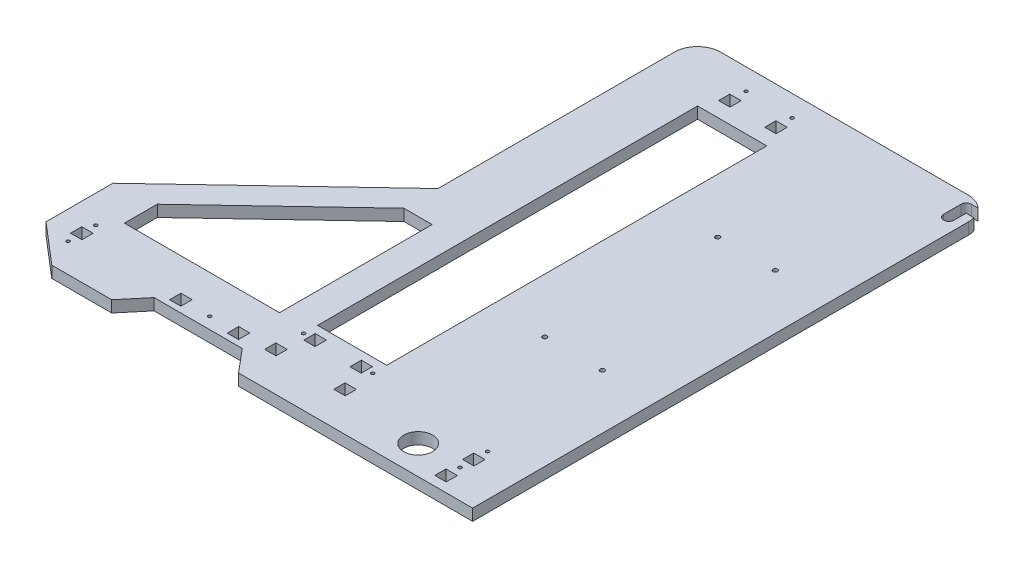
SolidWorks part; units mm, degrees
ref_plane "Front Plane" through (0, 0, 0) normal (0, 0, 1) x (1, 0, 0)
ref_plane "Top Plane" through (0, 0, 0) normal (0, 1, 0) x (1, 0, 0)
ref_plane "Right Plane" through (0, 0, 0) normal (1, 0, 0) x (0, 0, -1)
sketch "Sketch1" plane through (0, 0, 0) normal (0, 1, 0) x (1, 0, 0)
  line L0 (0, 0) -> (-235, 0)
  line L1 (-235, 0) -> (-235, -225)
  line L2 (-235, -225) -> (-380, -362)
  line L3 (-380, -362) -> (-380, -420)
  line L4 (-380, -420) -> (-345, -450)
  line L5 (-345, -450) -> (-293, -450)
  line L6 (-293, -450) -> (-263.6315, -415)
  line L7 (-263.6315, -415) -> (-212.3685, -415)
  line L8 (-212.3685, -415) -> (-183, -450)
  line L9 (-183, -450) -> (0, -450)
  line L10 (0, 0) -> (0, -450)
  line L12 (-293, -450) -> (-183, -450) construction
  dimension "D3" = 235
  dimension "D5" = 58
  dimension "D13" = 190
  dimension "D7" = 35
  dimension "D15" = 52
  dimension "D12" = 30
  dimension "D10" = 35
  dimension "D6" = 380
  dimension "D4" = 450
  dimension "D2" = 50
  dimension "D8" = 50
  dimension "D9" = 110
extrude "Boss-Extrude1" add sketch "Sketch1" along normal blind 10
sketch "Sketch16" plane through (0, 10, 0) normal (0, 1, 0) x (1, 0, 0)
  line L0 (0, -450) -> (20, -450)
  line L1 (20, -450) -> (20, 0)
  line L2 (20, 0) -> (0, 0)
  line L3 (0, 0) -> (0, -450)
  dimension "D1" = 20
  dimension "D2" = 90
extrude "Boss-Extrude2" add sketch "Sketch16" against normal through all
sketch "Sketch2" plane through (0, 10, 0) normal (0, 1, 0) x (1, 0, 0)
  line L0 (-235, -225) -> (-235, -415) construction
  line L1 (-263.6315, -415) -> (-212.3685, -415) construction
  line L2 (-345, -450) -> (-345, -328.931) construction
  line L3 (-235, -225) -> (-380, -362) construction
  line L4 (-345, -358.5097) -> (-235, -254.5787)
  line L5 (-235, -254.5787) -> (-210.5, -254.5787)
  line L6 (-210.5, -254.5787) -> (-210.5, -387)
  line L7 (-210.5, -387) -> (-345, -387)
  line L8 (-345, -387) -> (-345, -358.5097)
  line L9 (0, -450) -> (0, 0) construction
  line L10 (-184.5, -380) -> (-124.5, -380)
  line L11 (-184.5, -380) -> (-184.5, -50.425)
  line L12 (-184.5, -50.425) -> (-124.5, -50.425)
  line L13 (-124.5, -380) -> (-124.5, -50.425)
  line L14 (-124.5, -392.1) -> (-184.5, -392.1) construction
  line L15 (-16, -450) -> (-16, 0) construction
  line L16 (20, 0) -> (-235, 0) construction
  line L17 (-355.9, -440.6571) -> (-355.9, -339.2297) construction
  line L18 (-20.925, -441.85) -> (-11.075, -441.85)
  line L19 (-20.925, -441.85) -> (-20.925, -432.15)
  line L20 (-20.925, -432.15) -> (-11.075, -432.15)
  line L21 (-11.075, -441.85) -> (-11.075, -432.15)
  line L22 (-20.925, -441.85) -> (-11.075, -432.15) construction
  line L23 (-20.925, -432.15) -> (-11.075, -441.85) construction
  line L24 (-20.925, -417.85) -> (-11.075, -417.85)
  line L25 (-20.925, -417.85) -> (-20.925, -408.15)
  line L26 (-20.925, -408.15) -> (-11.075, -408.15)
  line L27 (-11.075, -417.85) -> (-11.075, -408.15)
  line L28 (-20.925, -417.85) -> (-11.075, -408.15) construction
  line L29 (-20.925, -408.15) -> (-11.075, -417.85) construction
  line L30 (-380, -420) -> (-345, -450) construction
  line L32 (-350.975, -408.15) -> (-360.825, -408.15)
  line L33 (-350.975, -408.15) -> (-350.975, -417.85)
  line L34 (-350.975, -417.85) -> (-360.825, -417.85)
  line L35 (-360.825, -408.15) -> (-360.825, -417.85)
  line L36 (-350.975, -408.15) -> (-360.825, -417.85) construction
  line L37 (-350.975, -417.85) -> (-360.825, -408.15) construction
  line L38 (-183, -450) -> (20, -450) construction
  line L39 (-183, -450) -> (20, -450) construction
  line L40 (-173.749, -32.425) -> (-113.749, -32.425) construction
  line L41 (-154.5, -50.425) -> (-154.5, -32.425) construction
  line L42 (-179.425, -27.575) -> (-169.575, -27.575)
  line L43 (-179.425, -27.575) -> (-179.425, -37.275)
  line L44 (-179.425, -37.275) -> (-169.575, -37.275)
  line L45 (-169.575, -27.575) -> (-169.575, -37.275)
  line L46 (-179.425, -27.575) -> (-169.575, -37.275) construction
  line L47 (-179.425, -37.275) -> (-169.575, -27.575) construction
  line L48 (-129.575, -37.275) -> (-139.425, -27.575) construction
  line L49 (-129.575, -27.575) -> (-139.425, -37.275) construction
  line L50 (-139.425, -27.575) -> (-139.425, -37.275)
  line L51 (-129.575, -37.275) -> (-139.425, -37.275)
  line L52 (-129.575, -27.575) -> (-129.575, -37.275)
  line L53 (-129.575, -27.575) -> (-139.425, -27.575)
  line L54 (-174.5, -32.425) -> (-174.5, -18.425) construction
  line L55 (-134.5, -32.425) -> (-134.5, -18.425) construction
  line L56 (-154.5, -380) -> (-154.5, -450) construction
  line L57 (-174.5, -392.1) -> (-134.5, -392.1) construction
  line L58 (-129.65, -397.025) -> (-139.35, -387.175) construction
  line L59 (-179.35, -387.175) -> (-169.65, -387.175)
  line L60 (-179.35, -387.175) -> (-179.35, -397.025)
  line L61 (-179.35, -397.025) -> (-169.65, -397.025)
  line L62 (-169.65, -387.175) -> (-169.65, -397.025)
  line L63 (-179.35, -387.175) -> (-169.65, -397.025) construction
  line L64 (-179.35, -397.025) -> (-169.65, -387.175) construction
  line L65 (-129.65, -387.175) -> (-139.35, -397.025) construction
  line L66 (-139.35, -387.175) -> (-139.35, -397.025)
  line L67 (-129.65, -397.025) -> (-139.35, -397.025)
  line L68 (-129.65, -387.175) -> (-129.65, -397.025)
  line L69 (-129.65, -387.175) -> (-139.35, -387.175)
  line L70 (-119.575, -420.95) -> (-129.425, -411.25) construction
  line L71 (-189.425, -411.25) -> (-179.575, -411.25)
  line L72 (-189.425, -411.25) -> (-189.425, -420.95)
  line L73 (-189.425, -420.95) -> (-179.575, -420.95)
  line L74 (-179.575, -411.25) -> (-179.575, -420.95)
  line L75 (-189.425, -411.25) -> (-179.575, -420.95) construction
  line L76 (-189.425, -420.95) -> (-179.575, -411.25) construction
  line L77 (-119.575, -411.25) -> (-129.425, -420.95) construction
  line L78 (-129.425, -411.25) -> (-129.425, -420.95)
  line L79 (-119.575, -420.95) -> (-129.425, -420.95)
  line L80 (-119.575, -411.25) -> (-119.575, -420.95)
  line L81 (-119.575, -411.25) -> (-129.425, -411.25)
  line L82 (-360.825, -408.15) -> (-11.075, -408.15) construction
  circle A0 centre (-16, -425) radius 1.45
  circle A1 centre (-16, -401) radius 1.45
  circle A2 centre (-355.9, -425) radius 1.45
  circle A3 centre (-355.9, -401) radius 1.45
  circle A4 centre (-174.5, -18.425) radius 1.45
  circle A5 centre (-134.5, -18.425) radius 1.45
  circle A6 centre (-124.5, -392.1) radius 1.45
  circle A7 centre (-184.5, -392.1) radius 1.45
  point P25 (-16, -437)
  point P30 (-16, -413)
  point P44 (-355.9, -413)
  point P61 (-174.5, -32.425)
  point P72 (-134.5, -32.425)
  point P85 (-174.5, -392.1)
  point P94 (-134.5, -392.1)
  point P95 (-184.5, -416.1)
  point P104 (-124.5, -416.1)
  point P105 (-154.5, -392.1)
  dimension "D13" = 2.9
  dimension "D14" = 2.9
  dimension "D23" = 2.9
  dimension "D24" = 2.9
  dimension "D31" = 2.9
  dimension "D37" = 2.9
  dimension "D1" = 21.5
  dimension "D2" = 28
  dimension "D3" = 24.5
  dimension "D4" = 60
  dimension "D7" = 26
  dimension "D8" = 9.7
  dimension "D9" = 9.85
  dimension "D10" = 9.85
  dimension "D11" = 9.7
  dimension "D12" = 24
  dimension "D15" = 24
  dimension "D19" = 9.85
  dimension "D20" = 9.7
  dimension "D26" = 12
  dimension "D27" = 9.85
  dimension "D28" = 9.7
  dimension "D33" = 9.7
  dimension "D38" = 9.85
  dimension "D39" = 9.7
  dimension "D41" = 24
  dimension "D34" = 30
  dimension "D36" = 12.1
  dimension "D30" = 18
  dimension "D29" = 40
  dimension "D17" = 13
  dimension "D32" = 14
  dimension "D35" = 20
  dimension "D16" = 12
  dimension "D21" = 90
  dimension "D25" = 24
  dimension "D5" = 359.75
  dimension "D22" = 349.75
  dimension "D40" = 30
  dimension "D6" = 70
  dimension "D42" = 0
  dimension "D43" = 0
  dimension "D18" = 16
  dimension "D44" = 9.85
extrude "Cut-Extrude1" cut sketch "Sketch2" against normal through all
fillet "Fillet1" radius 20 2 edges at (-235, 5, 0) (20, 5, 0)
sketch "Sketch11" plane through (0, 10, 0) normal (0, 1, 0) x (1, 0, 0)
  line L0 (-124.5, -215.2125) -> (20, -215.2125) construction
  line L1 (20, -450) -> (20, -20) construction
  line L3 (-52.25, -215.2125) -> (-52.25, -450) construction
  line L6 (-124.5, -380) -> (-124.5, -50.425) construction
  line L8 (-183, -450) -> (20, -450) construction
  circle A0 centre (-52.25, -425) radius 12.5
  circle A1 centre (-16, -425) radius 1.45 construction
  dimension "D1" = 25
  dimension "D2" = 0
  dimension "D3" = 0
extrude "WiringHole" cut sketch "Sketch11" against normal through all
sketch "Sketch9" plane through (0, 10, 0) normal (0, 1, 0) x (1, 0, 0)
  line L0 (-52.25, -412.5) -> (-52.25, 0) construction
  line L1 (0, 0) -> (-215, 0) construction
  line L2 (-124.5, -215.2125) -> (20, -215.2125) construction
  line L3 (-124.5, -380) -> (-124.5, -50.425) construction
  line L4 (-27.25, -140.2125) -> (-27.25, -290.2125) construction
  line L6 (-77.25, -140.2125) -> (-27.25, -140.2125) construction
  line L7 (-27.25, -290.2125) -> (-77.25, -290.2125) construction
  line L8 (-77.25, -290.2125) -> (-77.25, -140.2125) construction
  line L9 (20, -450) -> (20, -20) construction
  circle A0 centre (-52.25, -425) radius 12.5 construction
  circle A1 centre (-77.25, -140.2125) radius 1.95
  circle A2 centre (-27.25, -140.2125) radius 1.95
  circle A3 centre (-27.25, -290.2125) radius 1.95
  circle A4 centre (-77.25, -290.2125) radius 1.95
  dimension "D4" = 3.9
  dimension "D1" = 50
  dimension "D2" = 150
  dimension "D5" = 25
extrude "MountingHoles-PSU" cut sketch "Sketch9" against normal through all
sketch "Sketch10" [suppressed] plane through (0, 10, 0) normal (0, 1, 0) x (1, 0, 0)
  line L0 (-124.5, -215.2125) -> (20, -215.2125) construction
  line L1 (20, -450) -> (20, -20) construction
  line L2 (-52.25, -240.2125) -> (-22.25, -240.2125) construction
  line L3 (-37.25, -210.225) -> (-37.25, 0) construction
  line L4 (-52.25, -215.2125) -> (-52.25, -184.5972) construction
  line L7 (-124.5, -380) -> (-124.5, -50.425) construction
  line L8 (-52.25, -297.7125) -> (-22.25, -297.7125)
  line L9 (-52.25, -297.7125) -> (-52.25, -182.7125)
  line L10 (-52.25, -182.7125) -> (-22.25, -182.7125)
  line L11 (-22.25, -297.7125) -> (-22.25, -182.7125)
  line L12 (-52.25, -297.7125) -> (-22.25, -182.7125) construction
  line L13 (-52.25, -182.7125) -> (-22.25, -297.7125) construction
  line L15 (0, 0) -> (-215, 0) construction
  line L17 (-37.25, -210.225) -> (-37.25, -450) construction
  line L18 (-183, -450) -> (20, -450) construction
  line L19 (-64.75, -215.2125) -> (-39.75, -215.2125) construction
  line L20 (-37.25, -297.7125) -> (-37.25, -182.7125) construction
  dimension "D1" = 30
  dimension "D2" = 115
  dimension "D3" = 0
  dimension "D4" = 0
  dimension "D5" = 0
  dimension "D6" = 25
  dimension "D7" = 15
extrude "WiringSlot" [suppressed] cut sketch "Sketch10" against normal through all
sketch "CenterLines" [suppressed] plane through (0, 10, 0) normal (0, 1, 0) x (1, 0, 0)
  line L0 (-37.25, -297.7125) -> (-37.25, -182.7125) construction
  line L1 (-52.25, -297.7125) -> (-22.25, -297.7125) construction
  line L2 (-22.25, -182.7125) -> (-52.25, -182.7125) construction
  line L3 (-52.25, -240.2125) -> (-22.25, -240.2125) construction
  line L4 (-52.25, -182.7125) -> (-52.25, -297.7125) construction
  line L5 (-22.25, -297.7125) -> (-22.25, -182.7125) construction
ref_plane "Plane1" [suppressed] through (-37.25, 0, 0) normal (1, 0, 0) x (0, 0, -1)
sketch "Sketch6" [suppressed] plane through (0, 10, 0) normal (0, 1, 0) x (1, 0, 0)
  line L0 (-37.25, -297.7125) -> (-37.25, -182.7125) construction
  line L1 (-61.35, -237.7125) -> (-13.15, -237.7125) construction
  line L2 (-13.15, -192.9625) -> (-13.15, -275.4625) construction
  line L3 (-52.25, -297.7125) -> (-22.25, -297.7125) construction
  line L4 (-52.25, -235.2125) -> (-22.25, -235.2125) construction
  line L5 (-22.25, -182.7125) -> (-52.25, -182.7125) construction
  line L6 (-13.15, -192.9625) -> (-13.15, -199.9625) construction
  line L7 (-11.7, -192.9625) -> (-11.7, -199.9625)
  line L8 (-14.6, -192.9625) -> (-14.6, -199.9625)
  line L9 (-52.25, -240.2125) -> (-22.25, -240.2125) construction
  line L10 (-52.25, -182.7125) -> (-52.25, -297.7125) construction
  line L11 (-22.25, -297.7125) -> (-22.25, -182.7125) construction
  line L12 (-13.15, -282.4625) -> (-13.15, -275.4625) construction
  line L13 (-14.6, -282.4625) -> (-14.6, -275.4625)
  line L14 (-61.35, -275.4625) -> (-61.35, -199.9625) construction
  line L15 (-13.15, -282.4625) -> (-13.15, -199.9625) construction
  line L16 (-11.7, -282.4625) -> (-11.7, -275.4625)
  arc A2 (-11.7, -192.9625) -> (-14.6, -192.9625) centre (-13.15, -192.9625) ccw
  arc A3 (-14.6, -199.9625) -> (-11.7, -199.9625) centre (-13.15, -199.9625) ccw
  circle A4 centre (-61.35, -275.4625) radius 1.45
  circle A6 centre (-61.35, -199.9625) radius 1.45
  arc A8 (-14.6, -282.4625) -> (-11.7, -282.4625) centre (-13.15, -282.4625) ccw
  arc A9 (-11.7, -275.4625) -> (-14.6, -275.4625) centre (-13.15, -275.4625) ccw
  point P20 (-13.15, -196.4625)
  point P25 (-13.15, -278.9625)
  dimension "D8" = 2.9
  dimension "D12" = 2.9
  dimension "D4" = 1.45
  dimension "D5" = 1.45
  dimension "D11" = 82.5
  dimension "D14" = 75.5
  dimension "D2" = 24.1
  dimension "D3" = 48.2
  dimension "D6" = 2.5
  dimension "D9" = 7
  dimension "D10" = 7
extrude "MountingHoles-RAMPS" [suppressed] cut sketch "Sketch6" against normal through all
mirror "Mirror1" [suppressed] about plane through (-37.25, 0, 0) normal (1, 0, 0)
sketch "Sketch5" [suppressed] plane through (0, 10, 0) normal (0, 1, 0) x (1, 0, 0)
  line L0 (-22.25, -240.2125) -> (-52.25, -240.2125) construction
  line L3 (-22.25, -297.7125) -> (-22.25, -182.7125) construction
  line L5 (-52.25, -182.7125) -> (-52.25, -297.7125) construction
  line L7 (-16.25, -139.7125) -> (-58.25, -139.7125) construction
  line L8 (-16.25, -340.7125) -> (-58.25, -340.7125) construction
  line L9 (-37.25, -240.2125) -> (-37.25, -139.7125) construction
  line L10 (-37.25, -240.2125) -> (-37.25, -340.7125) construction
  circle A0 centre (-58.25, -139.7125) radius 1.45
  circle A1 centre (-16.25, -139.7125) radius 1.45
  circle A2 centre (-16.25, -340.7125) radius 1.45
  circle A3 centre (-58.25, -340.7125) radius 1.45
  point P17 (-37.25, -139.7125)
  point P22 (-37.25, -340.7125)
  dimension "D2" = 2.9
  dimension "D5" = 2.9
  dimension "D6" = 2.9
  dimension "D7" = 2.9
  dimension "D3" = 201
  dimension "D4" = 100.5
  dimension "D8" = 21
  dimension "D9" = 21
  dimension "D10" = 100.5
extrude "MountingHoles-Melzi" [suppressed] cut sketch "Sketch5" against normal through all
sketch "Sketch13" [suppressed] plane through (0, 0, 0) normal (0, -1, 0) x (-1, 0, 0)
  line L0 (52.25, -215.2125) -> (124.5, -215.2125) construction
  line L1 (124.5, -380) -> (124.5, -50.425) construction
  line L2 (82.25, -264.7275) -> (82.25, -165.6975) construction
  line L3 (37.25, -297.7125) -> (37.25, -182.7125) construction
  line L4 (52.25, -182.7125) -> (52.25, -297.7125) construction
  line L6 (82.25, -264.7275) -> (-15.65, -264.7275) construction
  circle A0 centre (82.25, -165.6975) radius 1.45
  circle A1 centre (82.25, -264.7275) radius 1.45
  circle A2 centre (-10.59, -172.1775) radius 1.45
  circle A3 centre (-15.65, -264.7275) radius 1.45
  point P11 (82.25, -215.2125)
  dimension "D8" = 2.9
  dimension "D6" = 2.9
  dimension "D1" = 2.9
  dimension "D2" = 49.515
  dimension "D3" = 45
  dimension "D4" = 6.48
  dimension "D5" = 92.84
  dimension "D7" = 97.9
extrude "Mountingholes-Smoothieboard" [suppressed] cut sketch "Sketch13" against normal through all
mirror "Flipped" [suppressed] about plane through (-37.25, 0, 0) normal (1, 0, 0)
sketch "Sketch21" [suppressed] plane through (0, 10, 0) normal (0, 1, 0) x (1, 0, 0)
  line L0 (-37.25, -182.7125) -> (-37.25, 0) construction
  line L1 (-22.25, -182.7125) -> (-52.25, -182.7125) construction
  line L2 (0, 0) -> (-215, 0) construction
  line L3 (-37.25, -94.7125) -> (-23.3697, -94.7125) construction
  circle A0 centre (-12.75, -65.7125) radius 1.45
  circle A1 centre (-61.75, -65.7125) radius 1.45
  circle A2 centre (-61.75, -123.7125) radius 1.45
  circle A3 centre (-12.75, -123.7125) radius 1.45
  circle A4 centre (-16.25, -139.7125) radius 1.45 construction
  dimension "D1" = 2.9
  dimension "D2" = 24.5
  dimension "D3" = 29
  dimension "D4" = 45
extrude "Pi" [suppressed] cut sketch "Sketch21" against normal through all
sketch "Sketch17" plane through (0, 10, 0) normal (0, 1, 0) x (1, 0, 0)
  line L0 (0, 0) -> (20, 0) construction
  line L1 (20, -23.6361) -> (20, 0) construction
  line L2 (20, -450) -> (20, -20) construction
  line L3 (20, -10) -> (8, -10) construction
  line L4 (20, -14.5) -> (8, -14.5)
  line L5 (20, -5.5) -> (8, -5.5)
  arc A0 (20, -14.5) -> (20, -5.5) centre (20, -10) ccw
  arc A1 (8, -5.5) -> (8, -14.5) centre (8, -10) ccw
  point P8 (14, -10)
  dimension "D1" = 9
  dimension "D2" = 12
  dimension "D3" = 10
extrude "Cut-Extrude3" cut sketch "Sketch17" against normal through all
sketch "Sketch18" plane through (0, 10, 0) normal (0, 1, 0) x (1, 0, 0)
  line L0 (8, -5.5) -> (8, -14.5) construction
  line L1 (3.5, -10) -> (8, -10) construction
  line L2 (8, -10) -> (8, -25) construction
  line L3 (12.5, -10) -> (12.5, -25)
  line L4 (3.5, -10) -> (3.5, -25)
  arc A0 (8, -5.5) -> (8, -14.5) centre (8, -10) ccw construction
  arc A1 (12.5, -10) -> (3.5, -10) centre (8, -10) ccw
  arc A2 (3.5, -25) -> (12.5, -25) centre (8, -25) ccw
  point P10 (8, -17.5)
  dimension "D1" = 9
  dimension "D2" = 0
  dimension "D3" = 15
extrude "Cut-Extrude4" cut sketch "Sketch18" against normal through all
sketch "Sketch19" plane through (0, 10, 0) normal (0, 1, 0) x (1, 0, 0)
  line L0 (-2, -25) -> (18, -25) construction
  line L1 (8, -25) -> (8, -5.5) construction
  circle A0 centre (18, -25) radius 1.45
  arc A1 (8, -5.5) -> (3.5, -10) centre (8, -10) ccw construction
  circle A2 centre (-2, -25) radius 1.45
  dimension "D2" = 2.9
extrude "Cut-Extrude5" [suppressed] cut sketch "Sketch19" against normal through all
sketch "Sketch22" plane through (0, 10, 0) normal (0, 1, 0) x (1, 0, 0)
  line L0 (-276.218, -430) -> (-199.782, -430)
  line L1 (-293, -450) -> (-263.6315, -415) construction
  line L2 (-212.3685, -415) -> (-183, -450) construction
  line L3 (-199.782, -430) -> (-212.3685, -415)
  line L4 (-212.3685, -415) -> (-263.6315, -415)
  line L5 (-263.6315, -415) -> (-276.218, -430)
  dimension "D1" = 15
extrude "Boss-Extrude3" add sketch "Sketch22" against normal through all
sketch "Sketch23" plane through (0, 10, 0) normal (0, 1, 0) x (1, 0, 0)
  line L0 (-238, -430) -> (-238, -387) construction
  line L1 (-276.218, -430) -> (-199.782, -430) construction
  line L2 (-345, -387) -> (-210.5, -387) construction
  line L3 (-213, -420) -> (-263, -420) construction
  line L4 (-179.35, -387.175) -> (-179.35, -397.025) construction
  line L5 (-267.85, -415.075) -> (-258.15, -415.075)
  line L6 (-267.85, -415.075) -> (-267.85, -424.925)
  line L7 (-267.85, -424.925) -> (-258.15, -424.925)
  line L8 (-258.15, -415.075) -> (-258.15, -424.925)
  line L9 (-267.85, -415.075) -> (-258.15, -424.925) construction
  line L10 (-267.85, -424.925) -> (-258.15, -415.075) construction
  line L11 (-208.15, -424.925) -> (-217.85, -415.075) construction
  line L12 (-208.15, -415.075) -> (-217.85, -424.925) construction
  line L13 (-217.85, -415.075) -> (-217.85, -424.925)
  line L14 (-208.15, -424.925) -> (-217.85, -424.925)
  line L15 (-208.15, -415.075) -> (-208.15, -424.925)
  line L16 (-208.15, -415.075) -> (-217.85, -415.075)
  circle A0 centre (-238, -420) radius 1.45
  point P19 (-238, -420)
  dimension "D4" = 2.9
  dimension "D1" = 9.7
  dimension "D3" = 10
extrude "Cut-Extrude6" cut sketch "Sketch23" against normal through all
equation "\"Y-ROD-SPACING\"=75"
equation "\"Y-BED-OFFSET\"=2"
equation "\"Y-BED-ROD-INSET\"=3.5"
equation "\"T-SLOT-NUT-FILLET-RADIUS\"=0.5"
equation "\"T-SLOT-SCREW-SHAFT-RADIUS\"=1.55"
equation "\"T-SLOT-SCREW-SHAFT-CUTOUT-LENGTH\"=11"
equation "\"T-SLOT-NUT-DEPTH\"=3.5"
equation "\"T-SLOT-NUT-WIDTH\"=2.85"
equation "\"T-SLOT-NUT-END-DISTANCE\"=8"
equation "\"ACRYLIC-TAB-CUTOUT-SIZE\"=\"ACRYLIC-THICKNESS\"+\"ACRYLIC-TAB-TOLERANCE\"*2"
equation "\"ACRYLIC-TAB-WIDTH\"=\"ACRYLIC-THICKNESS\""
equation "\"ACRYLIC-M3-HOLE\"=2.9"
equation "\"SMOOTHROD-CAP-SCREW-DISTANCE\"=20"
equation "\"FRAME-WIDTH-INNER\"=370"
equation "\"D24@Sketch2\"=\"ACRYLIC-M3-HOLE\""
equation "\"D23@Sketch2\"=\"ACRYLIC-M3-HOLE\""
equation "\"D19@Sketch2\"=\"ACRYLIC-THICKNESS\"-\"KERF\"*2"
equation "\"D20@Sketch2\"=\"ACRYLIC-TAB-WIDTH\"-\"KERF\"*4"
equation "\"D37@Sketch2\"=\"ACRYLIC-M3-HOLE\""
equation "\"D33@Sketch2\"=\"ACRYLIC-TAB-WIDTH\"-\"KERF\"*4"
equation "\"D38@Sketch2\"=\"ACRYLIC-THICKNESS\"-\"KERF\"*2"
equation "\"D39@Sketch2\"=\"ACRYLIC-TAB-WIDTH\"-\"KERF\"*4"
equation "\"D13@Sketch2\"=\"ACRYLIC-M3-HOLE\""
equation "\"D14@Sketch2\"=\"ACRYLIC-M3-HOLE\""
equation "\"D8@Sketch2\"=\"ACRYLIC-TAB-WIDTH\"-\"KERF\"*4"
equation "\"D9@Sketch2\"=\"ACRYLIC-THICKNESS\"-\"KERF\"*2"
equation "\"D10@Sketch2\"=\"ACRYLIC-THICKNESS\"-\"KERF\"*2"
equation "\"D11@Sketch2\"=\"ACRYLIC-TAB-WIDTH\"-\"KERF\"*4"
equation "\"D31@Sketch2\"=\"ACRYLIC-M3-HOLE\""
equation "\"D27@Sketch2\"=\"ACRYLIC-THICKNESS\"-\"KERF\"*2"
equation "\"D28@Sketch2\"=\"ACRYLIC-TAB-WIDTH\"-\"KERF\"*4"
equation "\"NEMA17-HOLE-SPACING\"=31"
equation "\"NEMA17-CENTRAL-CUTOUT\"=22.5"
equation "\"Z-BRACKET-REACH\"=57"
equation "\"TOP-BRACKET-SPACING\"=40"
equation "\"D29@Sketch2\"=\"TOP-BRACKET-SPACING\""
equation "\"ACRYLIC-THICKNESS\"=10"
equation "\"SMOOTHROD-Z-LENGTH\"=350"
equation "\"D5@Sketch2\"=\"SMOOTHROD-Z-LENGTH\"-\"SMOOTHROD-TIGHTENING-HEADROOM\"+10"
equation "\"SMOOTHROD-X-LENGTH\"=350"
equation "\"SMOOTHROD-Y-LENGTH\"=350"
equation "\"D22@Sketch2\"=\"SMOOTHROD-Y-LENGTH\"-\"SMOOTHROD-TIGHTENING-HEADROOM\""
equation "\"SMOOTHROD-TIGHTENING-HEADROOM\"=.25"
equation "\"X-ROD-SPACING\"=45"
equation "\"Z-ROD-SPACING\"=17.5"
equation "\"LEADSCREW-Z-LENGTH\"=300"
equation "\"SCREW-HEAD-RADIUS\"=6"
equation "\"PRINTED-X-SMOOTHROD-DIAMETER\"=8.8"
equation "\"PRINTED-X-SMOOTHROD-CUTOUT\"=10"
equation "\"PRINTED-X-BASE-HEIGHT\"=10"
equation "\"PRINTED-LM8UU-CUTOUT-SIZE\"=15.5"
equation "\"PRINTED-LM8UU-CUTOUT-LENGTH\"=24.5"
equation "\"PRINTED-X-IDLER-HEIGHT\"=16"
equation "\"PSU-MOUNTING-WIDTH\"=50"
equation "\"PSU-MOUNTING-HEIGHT\"=150"
equation "\"D1@Sketch9\"=\"PSU-MOUNTING-WIDTH\""
equation "\"D1@Boss-Extrude1\"=\"ACRYLIC-THICKNESS\""
equation "\"D6@Sketch1\"=\"SMOOTHROD-Y-LENGTH\"+30"
equation "\"D4@Sketch9\"=\"ACRYLIC-M4-HOLE\""
equation "\"D2@Sketch9\"=\"PSU-MOUNTING-HEIGHT\""
equation "\"D5@Sketch9\"=\"PSU-MOUNTING-WIDTH\"/2"
equation "\"D4@Sketch1\"=\"SMOOTHROD-Z-LENGTH\"+100"
equation "\"D8@Sketch6\"=\"ACRYLIC-M3-HOLE\""
equation "\"D12@Sketch6\"=\"ACRYLIC-M3-HOLE\""
equation "\"D2@Sketch5\"=\"ACRYLIC-M3-HOLE\""
equation "\"D5@Sketch5\"=\"ACRYLIC-M3-HOLE\""
equation "\"D6@Sketch5\"=\"ACRYLIC-M3-HOLE\""
equation "\"D7@Sketch5\"=\"ACRYLIC-M3-HOLE\""
equation "\"D1@Sketch13\"=\"ACRYLIC-M3-HOLE\""
equation "\"D6@Sketch13\"=\"ACRYLIC-M3-HOLE\""
equation "\"D8@Sketch13\"=\"ACRYLIC-M3-HOLE\""
equation "\"D4@Sketch6\"=\"ACRYLIC-M3-HOLE\"/2"
equation "\"D5@Sketch6\"=\"ACRYLIC-M3-HOLE\"/2"
equation "\"Y-BED-SCREW-SPACING\"=209"
equation "\"Y-BED-SCREW-CUTOUT-SLOT-HEIGHT\"=2.5"
equation "\"ACRYLIC-THICKNESS2\"=4.5"
equation "\"ACRYLIC-TAB-TOLERANCE\"=-.05"
equation "\"Z-ROD-INSET\"=13.5"
equation "\"SCREW-LENGTH-FRAME\"=\"ACRYLIC-THICKNESS\" + 10"
equation "\"SCREW-LENGTH-MOTOR\"=\"ACRYLIC-THICKNESS\" + 5"
equation "\"SCREW-LENGTH-EXTRUDER\"=28"
equation "\"Y-BELT-TO-ROD-DISTANCE\"=20"
equation "\"SPOOL-HOLDER-ROD-SPACING\"=150"
equation "\"ACRYLIC-X-CARRIAGE-WIDTH\"=55"
equation "\"ACRYLIC-X-CARRIAGE-HEIGHT\"=75"
equation "\"ACRYLIC-X-CARRIAGE-LM8UU-CUTOUT-WIDTH\"=24.25"
equation "\"ACRYLIC-X-CARRIAGE-SCREW-SPACING-X\"=15"
equation "\"ACRYLIC-X-CARRIAGE-SCREW-SPACING-Y\"=33"
equation "\"ACRYLIC-X-CARRIAGE-CENTER-TAB-SPACING\"=14"
equation "\"ACRYLIC-X-CARRIAGE-EXTRUDER-OFFSET\"=26"
equation "\"ACRYLIC-X-CARRIAGE-EXTRUDER-ANGLE\"=90"
equation "\"ACRYLIC-X-CARRIAGE-EXTRUDER-SHELF-DEPTH\"=\"ACRYLIC-X-CARRIAGE-EXTRUDER-OFFSET\" + 28"
equation "\"ACRYLIC-X-CARRIAGE-EXTRUDER-BRACE-SPACING\"=23"
equation "\"ACRYLIC-X-CARRIAGE-EXTRUDER-BRACE-TAB-OFFSET\"=20"
equation "\"ACRYLIC-X-CARRIAGE-EXTRUDER-BRACE-HEIGHT\"=35"
equation "\"ACRYLIC-X-CARRIAGE-EXTRUDER-BRACE-SCREW-SPACING\"=22"
equation "\"D1@Sketch19\"=\"SMOOTHROD-CAP-SCREW-DISTANCE\"/2"
equation "\"D2@Sketch19\"=\"ACRYLIC-M3-HOLE\""
equation "\"D1@Sketch21\"=\"ACRYLIC-M3-HOLE\""
equation "\"KERF\"=0.075"
equation "\"PRINTED-M3-HOLE\"=3.5"
equation "\"PRINTED-M3-NUT-AF\"=6.25"
equation "\"ACRYLIC-X-CARRIAGE-LM8UU-CUTOUT-HEIGHT\"=11.0"
equation "\"ACRYLIC-X-CARRIAGE-DUAL-WIDTH-MULTIPLIER\"=1.65"
equation "\"ACRYLIC-X-CARRIAGE-DUAL-HOTEND-SPACING\"=42"
equation "\"ACRYLIC-X-CARRIAGE-DUAL-WIDTH\"=75"
equation "\"ACRYLIC-X-CARRIAGE-DUAL-FAN-OFFSET\"=52"
equation "\"ACRYLIC-X-CARRIAGE-DUAL-FAN-HEIGHT\"=20"
equation "\"ACRYLIC-X-CARRIAGE-DUAL-HOTEND-SEPARATION\"=36"
equation "\"ACRYLIC-X-CARRIAGE-DUAL-MOUNT-PLATE-DEPTH\"=75"
equation "\"ACRYLIC-X-CARRIAGE-DUAL-MOUNT-BRACE-WIDTH\"=33"
equation "\"ACRYLIC-X-CARRIAGE-DUAL-MOUNT-SCREW-WIDTH\"=40"
equation "\"BLOWER-FAN-WIDTH\"=15"
equation "\"D44@Sketch2\"=\"ACRYLIC-THICKNESS\"-\"KERF\"*2"
equation "\"D1@Sketch23\"=10-\"KERF\"*4"
equation "\"D4@Sketch23\"=\"ACRYLIC-M3-HOLE\""
equation "\"ACRYLIC-THICKNESS-TAB-CUTOUT-WIDTH\"=\"ACRYLIC-THICKNESS\"-\"KERF\"*2"
equation "\"ACRYLIC-THICKNESS-TAB-CUTOUT-HEIGHT\"=\"ACRYLIC-TAB-WIDTH\"-\"KERF\"*4"
equation "\"ACRYLIC-THICKNESS2-TAB-CUTOUT-WIDTH\"=\"ACRYLIC-THICKNESS2\"-\"KERF\"*2"
equation "\"ACRYLIC-THICKNESS2-TAB-CUTOUT-HEIGHT\"=\"ACRYLIC-TAB-WIDTH\"-\"KERF\"*4"
equation "\"ACRYLIC-M4-HOLE\"=3.9"
